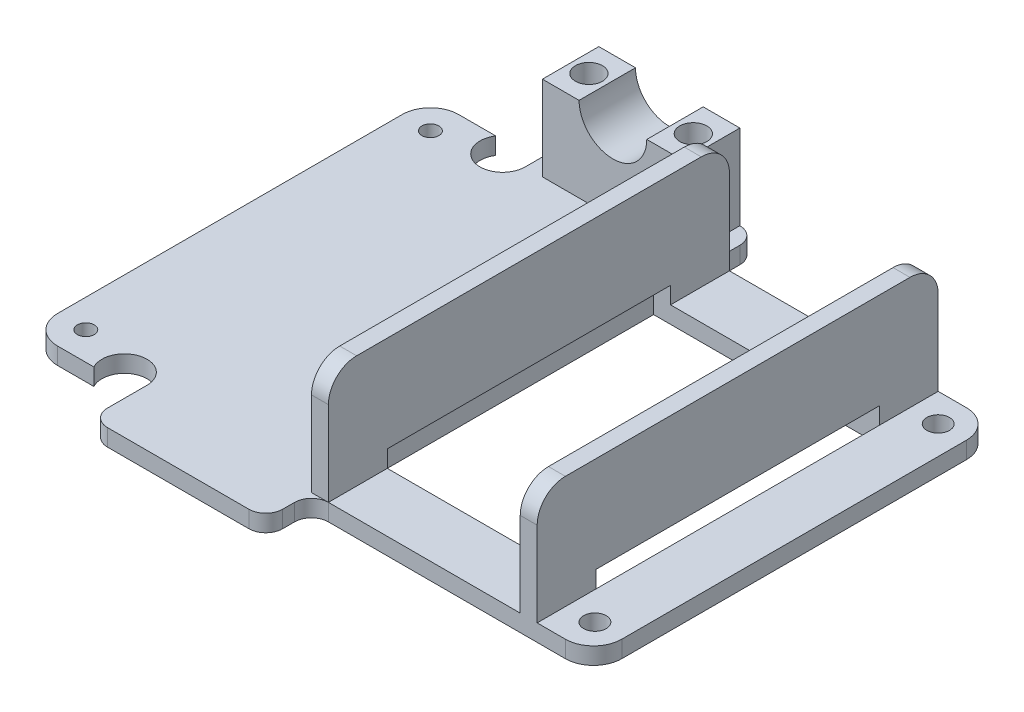
SolidWorks part; units mm, degrees
ref_plane "Front Plane" through (0, 0, 0) normal (0, 0, 1) x (1, 0, 0)
ref_plane "Top Plane" through (0, 0, 0) normal (0, 1, 0) x (1, 0, 0)
ref_plane "Right Plane" through (0, 0, 0) normal (1, 0, 0) x (0, 0, -1)
sketch "Sketch1" plane through (0, 0, 0) normal (0, 1, 0) x (1, 0, 0)
  line L0 (-50, 35.54) -> (50, 35.54)
  line L1 (-45, -30.54) -> (45, -30.54)
  line L2 (-45, -30.54) -> (-45, 30.54)
  line L3 (-45, 30.54) -> (45, 30.54)
  line L4 (45, -30.54) -> (45, 30.54)
  line L5 (-45, -30.54) -> (45, 30.54) construction
  line L6 (-45, 30.54) -> (45, -30.54) construction
  line L7 (50, -35.54) -> (50, 35.54)
  line L8 (-50, -35.54) -> (50, -35.54)
  line L9 (-50, -35.54) -> (-50, 35.54)
  point P0 (0, 0)
  dimension "D1" = 90
  dimension "D2" = 61.08
  dimension "D3" = 5
extrude "Boss-Extrude1" add sketch "Sketch1" along normal blind 3 contours L1 L4 L3 L2 | L9 L8 L7 L0 L4 L1 L2 L3 region at (0, 0, -34.3131) region at (0, 0, 0)
sketch "Sketch2" plane through (0, 3, 0) normal (0, 1, 0) x (1, 0, 0)
  line L4 (-45, -30.54) -> (45, -30.54)
  line L5 (45, -30.54) -> (45, 30.54)
  line L6 (45, 30.54) -> (-45, 30.54)
  line L7 (-45, 30.54) -> (-45, -30.54)
  line L8 (-45, -30.54) -> (45, -30.54)
  line L9 (45, -30.54) -> (45, 30.54)
  line L10 (45, 30.54) -> (-45, 30.54)
  line L11 (-45, 30.54) -> (-45, -30.54)
  circle A0 centre (-45, 30.54) radius 1.5
  circle A1 centre (-45, -30.54) radius 1.5
  circle A2 centre (45, 30.54) radius 2
  dimension "D2" = 61.08
  dimension "D3" = 90
  dimension "D1" = 0
extrude "Cut-Extrude1" cut sketch "Sketch2" against normal blind 10 contours A0 | A1 | A2
sketch "Sketch3" plane through (0, 3, 0) normal (0, 1, 0) x (1, 0, 0)
  circle A3 centre (45, -30.3043) radius 2.8
  circle A4 centre (45, -30.3043) radius 2.8
  dimension "D2" = 0
sketch "Sketch4" plane through (0, 3, 0) normal (0, 1, 0) x (1, 0, 0)
  circle A0 centre (45, -30.3043) radius 2
extrude "Cut-Extrude2" cut sketch "Sketch4" against normal blind 10
sketch "Sketch5" plane through (0, 3, 0) normal (0, 1, 0) x (1, 0, 0)
  line L0 (40, 35.54) -> (40, -35.54)
  line L1 (-50, 35.54) -> (50, 35.54) construction
  line L2 (-50, -35.54) -> (50, -35.54) construction
  line L3 (40, 35.54) -> (37, 35.54)
  line L4 (37, 35.54) -> (37, -35.54)
  line L5 (37, -35.54) -> (40, -35.54)
  line L6 (50, -35.54) -> (50, 35.54) construction
  line L7 (0, 35.54) -> (0, -35.54)
  line L8 (0, -35.54) -> (3, -35.54)
  line L9 (3, -35.54) -> (3, 35.54)
  line L10 (3, 35.54) -> (0, 35.54)
  dimension "D1" = 10
  dimension "D2" = 3
  dimension "D3" = 34
  dimension "D4" = 3
extrude "Boss-Extrude2" add sketch "Sketch5" along normal blind 20
sketch "Sketch6" plane through (50, 0, 0) normal (1, 0, 0) x (0, 0, -1)
  line L0 (-35.54, 3) -> (35.54, 3) construction
  line L1 (-25.1, 0) -> (25.1, 0)
  line L2 (-25.1, 0) -> (-25.1, 6)
  line L3 (-25.1, 6) -> (25.1, 6)
  line L4 (25.1, 0) -> (25.1, 6)
  line L5 (-25.1, 0) -> (25.1, 6) construction
  line L6 (-25.1, 6) -> (25.1, 0) construction
  point P0 (0, 3)
  dimension "D1" = 50.2
  dimension "D2" = 6
extrude "Cut-Extrude3" cut sketch "Sketch6" against normal blind 40 from offset 10 offset against normal yes
sketch "Sketch7" plane through (0, 0, 35.54) normal (0, 0, 1) x (1, 0, 0)
  line L1 (0, 23) -> (3, 23)
  line L2 (0, 23) -> (0, 3)
  line L3 (0, 3) -> (3, 3)
  line L4 (3, 23) -> (3, 3)
  line L5 (37, 23) -> (40, 23)
  line L6 (37, 23) -> (37, 3)
  line L7 (37, 3) -> (40, 3)
  line L8 (40, 23) -> (40, 3)
extrude "Boss-Extrude3" [suppressed] add sketch "Sketch7" along normal blind 20
sketch "Sketch8" plane through (0, 0, 25.1) normal (0, 0, -1) x (-1, 0, 0)
  line L1 (-37, 3) -> (-4, 3)
  line L2 (-37, 3) -> (-37, 8)
  line L3 (-37, 8) -> (-4, 1)
  line L4 (-4, 3) -> (-4, 1)
  dimension "D1" = 33
  dimension "D2" = 2
extrude "Boss-Extrude4" add sketch "Sketch8" along normal up to next rebuild error yes
sketch "Sketch10" plane through (0, 3, 0) normal (0, 1, 0) x (1, 0, 0)
  line L0 (-31.0539, 33.3885) -> (0, 33.3885)
  line L1 (0, 35.54) -> (0, -35.54) construction
  line L2 (0, 33.3885) -> (0, 35.54)
  line L3 (0, 35.54) -> (-31.6818, 35.54)
  line L4 (-50, 35.54) -> (0, 35.54) construction
  line L5 (-31.054, -33.641) -> (0, -33.641)
  line L6 (0, -25.1) -> (0, -35.54) construction
  line L7 (0, -33.641) -> (0, -35.54)
  line L8 (0, -35.54) -> (-31.5335, -35.54)
  line L9 (-50, -35.54) -> (0, -35.54) construction
  arc A0 (-31.6818, 35.54) -> (-31.0539, 33.3885) centre (-35.0539, 33.3885) ccw
  arc A1 (-31.054, -33.641) -> (-31.5335, -35.54) centre (-35.054, -33.641) ccw
  dimension "D1" = 8
  dimension "D2" = 8
extrude "Cut-Extrude5" cut sketch "Sketch10" against normal blind 20
fillet "Fillet1" radius 5 4 edges at (50, 1.5, 35.54) (50, 1.5, -35.54) (-50, 1.5, -35.54) (-50, 1.5, 35.54)
fillet "Fillet2" radius 5 4 edges at (1.5, 23, -35.54) (38.5, 23, -35.54) (38.5, 23, 35.54) (1.5, 23, 35.54)
sketch "Sketch13" plane through (0, 3, 0) normal (0, 1, 0) x (1, 0, 0)
  line L1 (-3, 33.3885) -> (-28, 33.3885)
  line L2 (-3, 33.3885) -> (-3, 23.3885)
  line L3 (-3, 23.3885) -> (-28, 23.3885)
  line L4 (-28, 33.3885) -> (-28, 23.3885)
  dimension "D1" = 25
  dimension "D2" = 10
extrude "Boss-Extrude6" add sketch "Sketch13" along normal blind 15
sketch "Sketch14" plane through (0, 0, -33.3885) normal (0, 0, -1) x (-1, 0, 0)
  line L0 (3, 18) -> (28, 18) construction
  circle A0 centre (15.5, 18) radius 6
  dimension "D1" = 12
extrude "Cut-Extrude7" cut sketch "Sketch14" against normal blind 15
sketch "Sketch16" plane through (0, 18, 0) normal (0, 1, 0) x (1, 0, 0)
  line L0 (-28, 33.3885) -> (-28, 23.3885) construction
  circle A0 centre (-6.25, 28.3885) radius 2.4
  circle A1 centre (-24.75, 28.3885) radius 2.4
  dimension "D1" = 3.25
extrude "Cut-Extrude8" cut sketch "Sketch16" against normal blind 10
sketch "Sketch17" plane through (0, 0, 33.641) normal (0, 0, 1) x (1, 0, 0)
  line L1 (-31.054, 3) -> (0, 3)
  line L2 (-31.054, 3) -> (-31.054, 0)
  line L3 (-31.054, 0) -> (0, 0)
  line L4 (0, 3) -> (0, 0)
extrude "Boss-Extrude7" add sketch "Sketch17" along normal blind 10
sketch "Sketch18" plane through (0, 0, -33.3885) normal (0, 0, -1) x (-1, 0, 0)
  line L1 (0, 3) -> (31.0539, 3)
  line L2 (0, 3) -> (0, 0)
  line L3 (0, 0) -> (31.0539, 0)
  line L4 (31.0539, 3) -> (31.0539, 0)
extrude "Boss-Extrude8" add sketch "Sketch18" along normal blind 10
pattern_linear "LPattern1" count 2 spacing 10 along (0, 0, -1) of "Boss-Extrude6", "Cut-Extrude7", "Cut-Extrude8"
sketch "Sketch19" plane through (0, 0, -23.3885) normal (0, 0, 1) x (1, 0, 0)
  line L1 (-28, 18) -> (-3, 18)
  line L2 (-28, 18) -> (-28, 3)
  line L3 (-28, 3) -> (-3, 3)
  line L4 (-3, 18) -> (-3, 3)
extrude "Cut-Extrude9" cut sketch "Sketch19" against normal blind 10
fillet "Fillet3" radius 3 5 edges at (0, 1.5, 35.54) (0, 1.5, 43.641) (-31.054, 1.5, 43.641) (-31.0539, 1.5, -43.3885) (0, 1.5, -43.3885)
